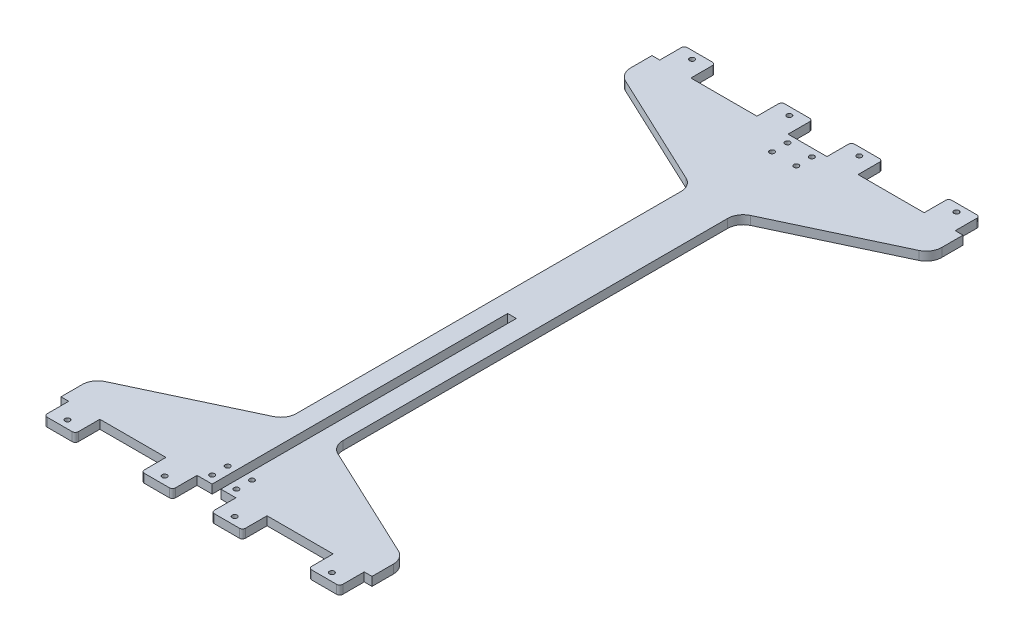
SolidWorks part; units mm, degrees
material "t5ハニカムプラダン"
ref_plane "正面" through (0, 0, 0) normal (0, 0, 1) x (1, 0, 0)
ref_plane "平面" through (0, 0, 0) normal (0, 1, 0) x (1, 0, 0)
ref_plane "右側面" through (0, 0, 0) normal (1, 0, 0) x (0, 0, -1)
sketch "ｽｹｯﾁ1" plane through (0, 0, 0) normal (0, 1, 0) x (1, 0, 0)
  line L0 (100, 380) -> (100, 0) construction
  line L1 (0, 0) -> (5, 0)
  line L2 (0, 0) -> (0, 380)
  line L3 (0, 380) -> (5, 380)
  line L4 (200, 0) -> (200, 380)
  line L5 (100, 190) -> (200, 190) construction
  line L6 (122.5, -15.8) -> (122.5, -10.8) construction
  line L7 (112.5, 0) -> (132.5, 0) construction
  line L8 (112.5, 0) -> (112.5, -13.8)
  line L9 (114.5, -15.8) -> (130.5, -15.8)
  line L10 (132.5, 0) -> (132.5, -13.8)
  line L11 (77.5, -15.8) -> (77.5, -10.8) construction
  line L12 (67.5, 0) -> (67.5, -13.8)
  line L13 (85.5, -15.8) -> (69.5, -15.8)
  line L14 (87.5, 0) -> (87.5, -13.8)
  line L15 (87.5, 0) -> (67.5, 0) construction
  line L16 (77.5, 395.8) -> (77.5, 390.8) construction
  line L17 (122.5, 395.8) -> (122.5, 390.8) construction
  line L18 (87.5, 380) -> (67.5, 380) construction
  line L19 (87.5, 380) -> (87.5, 393.8)
  line L20 (85.5, 395.8) -> (69.5, 395.8)
  line L21 (67.5, 380) -> (67.5, 393.8)
  line L22 (132.5, 380) -> (132.5, 393.8)
  line L23 (114.5, 395.8) -> (130.5, 395.8)
  line L24 (112.5, 380) -> (112.5, 393.8)
  line L25 (112.5, 380) -> (132.5, 380) construction
  line L26 (67.5, 380) -> (87.5, 380) construction
  line L27 (87.5, 380) -> (112.5, 380)
  line L28 (112.5, 380) -> (132.5, 380) construction
  line L29 (132.5, 380) -> (175, 380)
  line L30 (67.5, 0) -> (87.5, 0) construction
  line L31 (87.5, 0) -> (97.2, 0)
  line L32 (112.5, 0) -> (132.5, 0) construction
  line L33 (132.5, 0) -> (175, 0)
  line L34 (100, 0) -> (102.8, 0) construction
  line L35 (97.2, 0) -> (100, 0) construction
  line L36 (97.2, 0) -> (97.2, 190)
  line L37 (97.2, 190) -> (102.8, 190)
  line L38 (102.8, 0) -> (102.8, 190)
  line L39 (100, 0) -> (102.8, 0) construction
  line L40 (102.8, 0) -> (112.5, 0)
  line L41 (97.2, 0) -> (100, 0) construction
  line L42 (107.8, 375) -> (107.8, 365) construction
  line L43 (175, 0) -> (175, -13.8)
  line L44 (177, -15.8) -> (193, -15.8)
  line L45 (195, 0) -> (195, -13.8)
  line L46 (185, -15.8) -> (185, -10.8) construction
  line L47 (175, 0) -> (195, 0) construction
  line L48 (175, 0) -> (195, 0) construction
  line L49 (175, 380) -> (195, 380) construction
  line L50 (175, 380) -> (195, 380) construction
  line L51 (185, 395.8) -> (185, 390.8) construction
  line L52 (195, 380) -> (195, 393.8)
  line L53 (177, 395.8) -> (193, 395.8)
  line L54 (175, 380) -> (175, 393.8)
  line L55 (25, 0) -> (5, 0) construction
  line L56 (25, 0) -> (5, 0) construction
  line L57 (15, -15.8) -> (15, -10.8) construction
  line L58 (5, 0) -> (5, -13.8)
  line L59 (23, -15.8) -> (7, -15.8)
  line L60 (25, 0) -> (25, -13.8)
  line L61 (15, 395.8) -> (15, 390.8) construction
  line L62 (25, 380) -> (5, 380) construction
  line L63 (25, 380) -> (5, 380) construction
  line L64 (25, 380) -> (25, 393.8)
  line L65 (23, 395.8) -> (7, 395.8)
  line L66 (5, 380) -> (5, 393.8)
  line L67 (5, 0) -> (25, 0) construction
  line L68 (25, 0) -> (67.5, 0)
  line L69 (175, 0) -> (195, 0) construction
  line L70 (195, 0) -> (200, 0)
  line L71 (5, 380) -> (25, 380) construction
  line L72 (25, 380) -> (67.5, 380)
  line L73 (175, 380) -> (195, 380) construction
  line L74 (195, 380) -> (200, 380)
  circle A0 centre (122.5, -10.8) radius 1.6
  arc A1 (130.5, -15.8) -> (132.5, -13.8) centre (130.5, -13.8) ccw
  arc A2 (112.5, -13.8) -> (114.5, -15.8) centre (114.5, -13.8) ccw
  arc A3 (87.5, -13.8) -> (85.5, -15.8) centre (85.5, -13.8) cw
  arc A4 (69.5, -15.8) -> (67.5, -13.8) centre (69.5, -13.8) cw
  circle A5 centre (77.5, -10.8) radius 1.6
  circle A6 centre (77.5, 390.8) radius 1.6
  arc A7 (69.5, 395.8) -> (67.5, 393.8) centre (69.5, 393.8) ccw
  arc A8 (87.5, 393.8) -> (85.5, 395.8) centre (85.5, 393.8) ccw
  arc A9 (112.5, 393.8) -> (114.5, 395.8) centre (114.5, 393.8) cw
  arc A10 (130.5, 395.8) -> (132.5, 393.8) centre (130.5, 393.8) cw
  circle A11 centre (122.5, 390.8) radius 1.6
  circle A12 centre (107.8, 375) radius 1.6
  circle A13 centre (92.2, 375) radius 1.6
  circle A14 centre (107.8, 5) radius 1.6
  circle A15 centre (92.2, 5) radius 1.6
  circle A16 centre (107.8, 365) radius 1.6
  circle A17 centre (92.2, 365) radius 1.6
  circle A18 centre (107.8, 15) radius 1.6
  circle A19 centre (92.2, 15) radius 1.6
  circle A20 centre (185, -10.8) radius 1.6
  arc A21 (193, -15.8) -> (195, -13.8) centre (193, -13.8) ccw
  arc A22 (175, -13.8) -> (177, -15.8) centre (177, -13.8) ccw
  arc A23 (175, 393.8) -> (177, 395.8) centre (177, 393.8) cw
  arc A24 (193, 395.8) -> (195, 393.8) centre (193, 393.8) cw
  circle A25 centre (185, 390.8) radius 1.6
  arc A26 (25, -13.8) -> (23, -15.8) centre (23, -13.8) cw
  arc A27 (7, -15.8) -> (5, -13.8) centre (7, -13.8) cw
  circle A28 centre (15, -10.8) radius 1.6
  circle A29 centre (15, 390.8) radius 1.6
  arc A30 (7, 395.8) -> (5, 393.8) centre (7, 393.8) ccw
  arc A31 (25, 393.8) -> (23, 395.8) centre (23, 393.8) ccw
  point P18 (132.5, -15.8)
  point P21 (112.5, -15.8)
  point P33 (87.5, -15.8)
  point P34 (67.5, -15.8)
  point P57 (67.5, 395.8)
  point P58 (87.5, 395.8)
  point P59 (112.5, 395.8)
  point P60 (132.5, 395.8)
  dimension "D5" = 3.2
  dimension "D7" = 2
  dimension "D10" = 3.2
  dimension "D1" = 200
  dimension "D2" = 380
  dimension "D3" = 20
  dimension "D4" = 15.8
  dimension "D6" = 5
  dimension "D8" = 25
  dimension "D9" = 5.6
  dimension "D11" = 5
  dimension "D12" = 5
  dimension "D13" = 10
  dimension "D15" = 5
  dimension "D14" = 2
extrude "ﾎﾞｽ - 押し出し1" add sketch "ｽｹｯﾁ1" along normal blind 5.6
sketch "ｽｹｯﾁ2" plane through (0, 5.6, 0) normal (0, 1, 0) x (1, 0, 0)
  line L0 (100, 380) -> (100, 190) construction
  line L1 (112.5, 380) -> (87.5, 380) construction
  line L2 (97.2, 190) -> (102.8, 190) construction
  line L3 (100, 190) -> (200, 190) construction
  line L4 (200, 0) -> (200, 380) construction
  line L5 (132.5, 0) -> (175, 0) construction
  line L6 (200, 60) -> (115, 60)
  line L7 (200, 60) -> (200, 320)
  line L8 (200, 320) -> (115, 320)
  line L9 (115, 60) -> (115, 320)
  line L10 (85, 60) -> (85, 320)
  line L11 (0, 320) -> (85, 320)
  line L12 (0, 60) -> (0, 320)
  line L13 (0, 60) -> (85, 60)
  line L14 (115, 60) -> (200, 20)
  line L15 (200, 0) -> (200, 380) construction
  line L16 (200, 20) -> (200, 60)
  line L17 (85, 60) -> (0, 20)
  line L18 (115, 320) -> (200, 360)
  line L19 (85, 320) -> (0, 360)
  line L20 (200, 60) -> (200, 20)
  line L21 (200, 320) -> (200, 360)
  line L22 (0, 360) -> (0, 320)
  line L23 (0, 60) -> (0, 20)
  dimension "D1" = 60
  dimension "D2" = 30
  dimension "D3" = 20
extrude "ｶｯﾄ - 押し出し1" cut sketch "ｽｹｯﾁ2" against normal through all contours L12 L13 L10 L11 | L19 L22 L11 | L13 L23 L17 | L14 L16 L6 | L9 L6 L7 L8 | L8 L21 L18 region at (171.6667, 5.6, -46.6667) region at (157.5, 5.6, -190) region at (171.6667, 5.6, -333.3333) region at (42.5, 5.6, -190) region at (28.3333, 5.6, -46.6667) region at (28.3333, 5.6, -333.3333)
fillet "ﾌｨﾚｯﾄ1" radius 10 8 edges at (200, 2.8, -360) (115, 2.8, -320) (0, 2.8, -360) (85, 2.8, -320) (85, 2.8, -60) (0, 2.8, -20) (200, 2.8, -20) (115, 2.8, -60)
